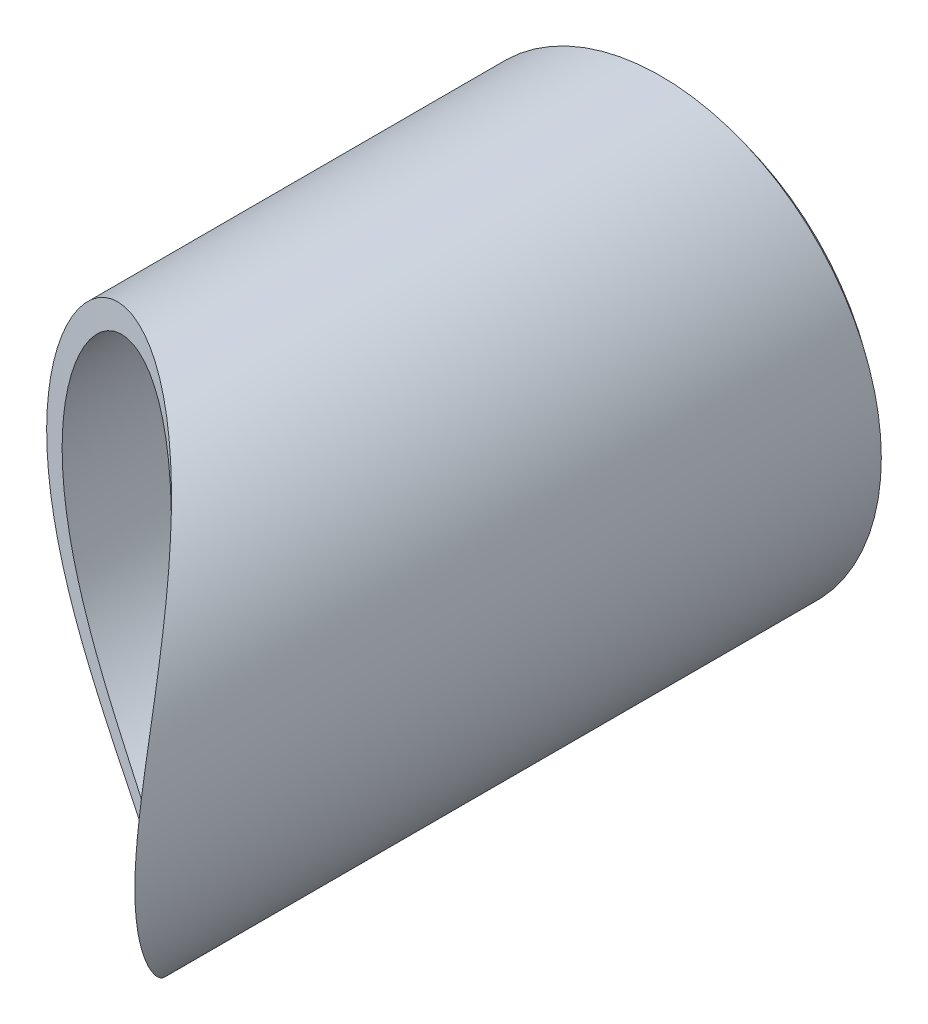
SolidWorks part; units mm, degrees
material "Plain Carbon Steel"
ref_plane "Front Plane" through (0, 0, 0) normal (0, 0, 1) x (1, 0, 0)
ref_plane "Top Plane" through (0, 0, 0) normal (0, 1, 0) x (1, 0, 0)
ref_plane "Right Plane" through (0, 0, 0) normal (1, 0, 0) x (0, 0, -1)
sketch "Sketch1" plane through (0, 0, 0) normal (0, 0, 1) x (1, 0, 0)
  circle A0 centre (0, 0) radius 57.15
  circle A1 centre (0, 0) radius 51.1302
  dimension "D1" = 114.3
  dimension "D2" = 6.0198
extrude "Extrude1" add sketch "Sketch1" along normal mid plane 196.85
chamfer "Chamfer1" [suppressed] distance 1.8542 angle 37
chamfer "Chamfer2" [suppressed] distance 1.8542 angle 37
sketch "Sketch2" [suppressed] plane through (0, 0, 0) normal (1, 0, 0) x (0, 0, -1)
  line L0 (-762, 52.6542) -> (-762, -52.6542) construction
  point P0 (-762, 0)
ref_plane "Plane-Origin" through (0, 0, 0) normal (0, 0, 1) x (1, 0, 0)
ref_plane "Plane-Extruded" [suppressed] through (0, 0, 762) normal (0, 0, 1) x (1, 0, 0)
ref_axis "Axis1" through (0, 0, 98.425) along (0, 0, -1)
ref_plane "Plane1" [suppressed] through (-6.3769, 37.5626, 38.1) normal (0.1183, -0.6971, -0.7071) x (-0.993, -0.0832, -0.0842)
sketch "Sketch3" [suppressed] plane through (-6.3769, 37.5626, 38.1) normal (0.1183, -0.6971, -0.7071) x (-0.993, -0.0832, -0.0842)
  line L0 (-157.7314, -35.3522) -> (144.9003, -71.6442) construction
  line L1 (-157.7314, -35.3522) -> (144.9003, -71.6442) construction
ref_plane "Plane2" [suppressed] through (6.3769, -37.5626, 38.1) normal (0.1183, -0.6971, 0.7071) x (0.993, 0.0831, -0.0843)
sketch "Sketch4" plane through (0, 0, 0) normal (0, 1, 0) x (1, 0, 0)
  line L0 (57.15, -98.425) -> (57.15, -156.1406) construction
  line L1 (-57.15, -6.985) -> (-57.15, -98.425)
  line L2 (-57.15, 98.425) -> (-57.15, -98.425) construction
  line L3 (-57.15, -98.425) -> (57.15, -98.425)
  arc A1 (-57.15, -6.985) -> (57.15, -98.425) centre (-118.5069, -200.8386) cw
  dimension "D1" = 91.44
extrude "Cut-Extrude1" cut sketch "Sketch4" along normal through all both and the other way through all
chamfer "Chamfer4" distance 4.445 angle 37.5 1 edges at (57.15, 0, -98.425) first distance on face at (57.15, 0, -98.425)
